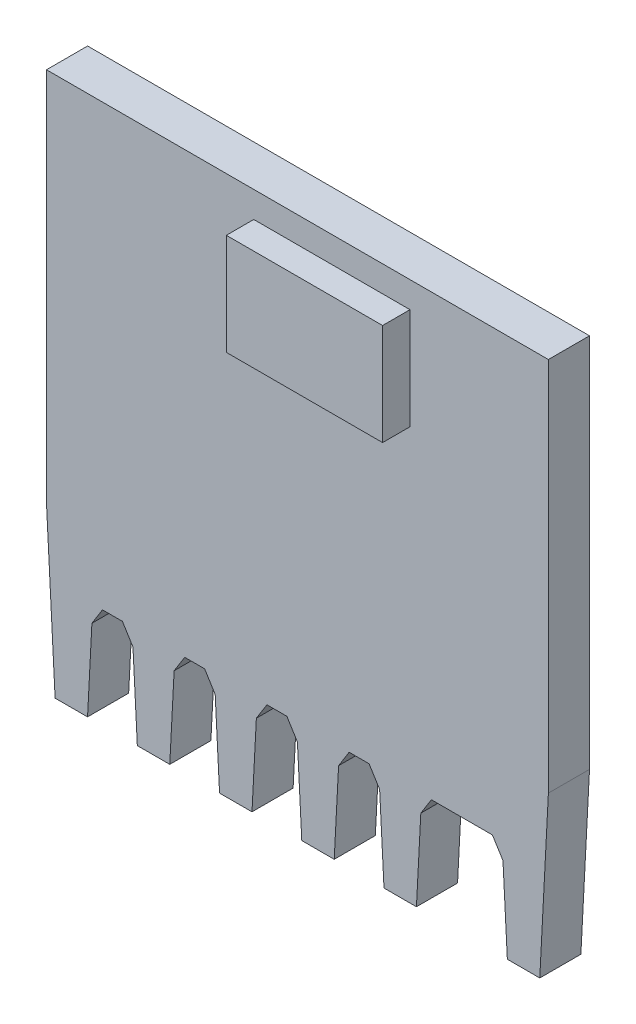
SolidWorks part; units mm, degrees
ref_plane "Front Plane" through (0, 0, 0) normal (0, 0, 1) x (1, 0, 0)
ref_plane "Top Plane" through (0, 0, 0) normal (0, 1, 0) x (1, 0, 0)
ref_plane "Right Plane" through (0, 0, 0) normal (1, 0, 0) x (0, 0, -1)
sketch "Sketch1" plane through (0, 0, 0) normal (0, 0, 1) x (1, 0, 0)
  line L0 (0, 0) -> (0, 19.7) construction
  line L1 (0, 19.7) -> (18.3124, 19.7) construction
  line L2 (18.3124, 19.7) -> (18.3124, 0) construction
  line L3 (18.3124, 0) -> (0, 0) construction
  line L4 (0, 3) -> (18.3124, 3) construction
  line L5 (0, 6) -> (18.3124, 6) construction
  line L6 (0.9062, 6) -> (0.9062, 0) construction
  line L7 (3.9062, 6) -> (3.9062, 0) construction
  line L8 (6.9062, 6) -> (6.9062, 0) construction
  line L9 (9.9062, 6) -> (9.9062, 0) construction
  line L10 (12.9062, 6) -> (12.9062, 0) construction
  line L11 (17.4062, 6) -> (17.4062, 0) construction
  line L12 (0.9062, 3) -> (3.9062, 3) construction
  line L13 (3.9062, 3) -> (6.9062, 3) construction
  line L14 (6.9062, 3) -> (9.9062, 3) construction
  line L15 (9.9062, 3) -> (12.9062, 3) construction
  line L16 (12.9062, 3) -> (17.4062, 3) construction
  line L17 (0.9062, 3) -> (0, 3) construction
  line L18 (17.4062, 3) -> (18.3124, 3) construction
  line L19 (2.4062, 3) -> (2.4062, 0) construction
  line L20 (5.4062, 3) -> (5.4062, 0) construction
  line L21 (8.4062, 3) -> (8.4062, 0) construction
  line L22 (11.4062, 3) -> (11.4062, 0) construction
  line L23 (15.1562, 3) -> (15.1562, 0) construction
  line L24 (14.4062, 3.75) -> (15.9062, 3.75) construction
  line L25 (0, 6) -> (0.3144, 0)
  line L26 (0.3144, 0) -> (1.4979, 0)
  line L27 (1.4979, 0) -> (1.6572, 3.0393)
  line L28 (3.1552, 3.0393) -> (3.3144, 0)
  line L29 (3.3144, 0) -> (4.4979, 0)
  line L30 (4.4979, 0) -> (4.6572, 3.0393)
  line L31 (6.1552, 3.0393) -> (6.3144, 0)
  line L32 (6.3144, 0) -> (7.4979, 0)
  line L33 (7.4979, 0) -> (7.6572, 3.0393)
  line L34 (9.1552, 3.0393) -> (9.3144, 0)
  line L35 (9.3144, 0) -> (10.4979, 0)
  line L36 (10.4979, 0) -> (10.6572, 3.0393)
  line L37 (12.1552, 3.0393) -> (12.3144, 0)
  line L38 (12.3144, 0) -> (13.4979, 0)
  line L39 (13.4979, 0) -> (13.6572, 3.0393)
  line L40 (16.6552, 3.0393) -> (16.8144, 0)
  line L41 (16.8144, 0) -> (17.9979, 0)
  line L42 (17.9979, 0) -> (18.3124, 6)
  line L44 (1.6572, 3.0393) -> (2.0426, 3.656)
  line L45 (0, 6) -> (0, 19.7)
  line L46 (0, 19.7) -> (18.3124, 19.7)
  line L47 (18.3124, 19.7) -> (18.3124, 6)
  line L48 (9.1562, 19.7) -> (9.1562, 6) construction
  line L49 (2.0426, 3.656) -> (2.7698, 3.656)
  line L50 (2.7698, 3.656) -> (3.1552, 3.0393)
  line L51 (4.6572, 3.0393) -> (5.0426, 3.656)
  line L52 (5.0426, 3.656) -> (5.7698, 3.656)
  line L53 (5.7698, 3.656) -> (6.1552, 3.0393)
  line L54 (7.6572, 3.0393) -> (8.0426, 3.656)
  line L55 (8.0426, 3.656) -> (8.7698, 3.656)
  line L56 (8.7698, 3.656) -> (9.1552, 3.0393)
  line L57 (10.6572, 3.0393) -> (11.0426, 3.656)
  line L58 (11.0426, 3.656) -> (11.7698, 3.656)
  line L59 (11.7698, 3.656) -> (12.1552, 3.0393)
  line L60 (13.6572, 3.0393) -> (14.0426, 3.656)
  line L61 (14.0426, 3.656) -> (16.2698, 3.656)
  line L62 (16.2698, 3.656) -> (16.6552, 3.0393)
  arc A0 (3.1552, 3.0393) -> (1.6572, 3.0393) centre (2.4062, 3) ccw construction
  arc A1 (6.1552, 3.0393) -> (4.6572, 3.0393) centre (5.4062, 3) ccw construction
  arc A2 (9.1552, 3.0393) -> (7.6572, 3.0393) centre (8.4062, 3) ccw construction
  arc A3 (12.1552, 3.0393) -> (10.6572, 3.0393) centre (11.4062, 3) ccw construction
  arc A4 (13.6572, 3.0393) -> (14.4062, 3.75) centre (14.4062, 3) cw construction
  arc A5 (16.6552, 3.0393) -> (15.9062, 3.75) centre (15.9062, 3) ccw construction
  dimension "D7" = 0.75
  dimension "D1" = 3
  dimension "D2" = 6
  dimension "D3" = 13.7
  dimension "D4" = 3
  dimension "D6" = 4.5
  dimension "D8" = 3
  dimension "D9" = 18.3124
  dimension "D10" = 19.7
extrude "Boss-Extrude1" add sketch "Sketch1" along normal blind 1.5
sketch "Sketch3" plane through (0, 0, 0) normal (0, 0, 1) x (1, 0, 0)
  line L0 (-0.4005, 6) -> (18.7129, 6)
  line L1 (18.7129, 3) -> (-0.4005, 3) construction
  line L2 (-0.4005, 0) -> (18.7129, 0) construction
  line L3 (-0.4005, -0.5) -> (18.7129, -0.5) construction
  line L4 (18.7129, -0.5) -> (18.7129, 6) construction
  line L5 (-0.4005, 6) -> (-0.4005, -0.5) construction
  line L6 (18.3124, 0) -> (0, 0) construction
  line L7 (0, 3) -> (18.3124, 3) construction
  line L8 (0, 6) -> (18.3124, 6) construction
  line L9 (0.3407, -0.5) -> (0, 6) construction
  line L10 (18.3124, 6) -> (17.9717, -0.5) construction
  line L11 (17.9979, 0) -> (18.3124, 6) construction
  line L12 (0, 6) -> (0.3144, 0) construction
  line L13 (5.4062, 6) -> (5.4062, -0.5) construction
  line L14 (3.9062, 6) -> (3.9062, -0.5) construction
  line L15 (5.4062, 3) -> (5.4062, 0) construction
  line L16 (3.1572, 3) -> (3.3407, -0.5) construction
  line L17 (2.7567, 3) -> (2.9401, -0.5)
  line L18 (3.1552, 3.0393) -> (3.3144, 0) construction
  line L19 (2.9401, -0.5) -> (4.8723, -0.5)
  line L20 (4.8723, -0.5) -> (5.0557, 3)
  line L21 (2.8484, 1.25) -> (3.2478, 1.2709) construction
  line L22 (5.9401, -0.5) -> (5.7567, 3)
  line L26 (7.8723, -0.5) -> (5.9401, -0.5)
  line L27 (8.0557, 3) -> (7.8723, -0.5)
  line L30 (2.4062, -0.5) -> (2.4062, 6) construction
  line L31 (2.4062, 3) -> (2.4062, 0) construction
  line L32 (8.4062, 6) -> (8.4062, -0.5) construction
  line L34 (11.4062, -0.5) -> (11.4062, 6) construction
  line L35 (15.1562, -0.5) -> (15.1562, 6) construction
  line L36 (8.4062, 3) -> (8.4062, 0) construction
  line L37 (11.4062, 3) -> (11.4062, 0) construction
  line L38 (15.1562, 3) -> (15.1562, 0) construction
  line L39 (10.8723, -0.5) -> (11.0557, 3)
  line L40 (8.9401, -0.5) -> (10.8723, -0.5)
  line L41 (8.7567, 3) -> (8.9401, -0.5)
  line L42 (11.9401, -0.5) -> (11.7567, 3)
  line L43 (13.8723, -0.5) -> (11.9401, -0.5)
  line L44 (14.0557, 3) -> (13.8723, -0.5)
  line L45 (16.4401, -0.5) -> (18.3723, -0.5)
  line L46 (16.2567, 3) -> (16.4401, -0.5)
  line L47 (18.3723, -0.5) -> (18.7129, 6)
  line L48 (1.8723, -0.5) -> (-0.0599, -0.5)
  line L49 (2.0557, 3) -> (1.8723, -0.5)
  line L50 (-0.0599, -0.5) -> (-0.4005, 6)
  line L51 (16.2567, 3) -> (14.0557, 3)
  line L52 (11.7567, 3) -> (11.0557, 3)
  line L53 (8.7567, 3) -> (8.0557, 3)
  line L54 (5.7567, 3) -> (5.0557, 3)
  line L55 (2.7567, 3) -> (2.0557, 3)
  dimension "D1" = 0.5
  dimension "D2" = 0.4
ref_plane "Plane1" through (3.9062, 0, 0) normal (1, 0, 0) x (0, 0, -1)
sketch "Sketch4" plane through (3.9062, 0, 0) normal (1, 0, 0) x (0, 0, -1)
  line L0 (0, 6) -> (0, -0.5) construction
  line L1 (0.6, 6) -> (-2.1, 6) construction
  line L2 (0.6, 6) -> (0.6, -0.5) construction
  line L3 (0.6, -0.5) -> (-2.1, -0.5) construction
  line L4 (-2.1, 6) -> (-2.1, -0.5) construction
  line L5 (-0.75, -0.5) -> (-0.75, 6) construction
  line L6 (-1.5, 6) -> (-1.5, -0.5) construction
  line L7 (0.6, 2.4005) -> (-2.1, 2.4005) construction
  line L8 (0.3, 6) -> (0.3, -0.5) construction
  line L9 (0.6, 2.4005) -> (3.846, 6) construction
  line L10 (2.2302, 6) -> (0.6, 4.1923) construction
  line L11 (0.6, 4.1923) -> (1.7139, 3.1878) construction
  line L12 (1.7139, 3.1878) -> (4.25, 6)
  line L13 (4.25, 6) -> (0.6, 6) construction
  line L14 (0.3, 1) -> (-1.8, 1) construction
  line L15 (-2.1, 0) -> (0.6, 0) construction
  line L16 (1.7139, 3.1878) -> (1.4912, 3.3887)
  line L17 (1.4912, 3.3887) -> (0.6, 2.4005)
  line L18 (-3.2139, 3.1878) -> (-5.75, 6)
  line L19 (-3.2139, 3.1878) -> (-2.9912, 3.3887)
  line L20 (-2.9912, 3.3887) -> (-2.1, 2.4005)
  line L21 (-2.1, 6) -> (-5.75, 6) construction
  line L22 (0.6, 3.0724) -> (3.2401, 6) construction
  arc A0 (0.4965, 2.2224) -> (0.6, -0.5) centre (4.2, 1) ccw
  arc A1 (0.6, 2.4005) -> (0.4965, 2.2224) centre (0.9713, 2.0656) ccw
  arc A2 (-2.1, 2.4005) -> (-1.9965, 2.2224) centre (-2.4713, 2.0656) cw
  arc A3 (-1.9965, 2.2224) -> (-2.1, -0.5) centre (-5.7, 1) cw
  dimension "D6" = 0.5
  dimension "D1" = 0.6
  dimension "D2" = 0.3
  dimension "D3" = 1.5
  dimension "D4" = 1
  dimension "D5" = 0.3
  dimension "D7" = 10
sketch "Sketch5" plane through (0, 0, 0) normal (1, 0, 0) x (0, 0, -1)
  line L0 (2.2302, 6) -> (0.6, 4.1923) construction
  line L1 (0.6, 4.1923) -> (1.7139, 3.1878) construction
  line L2 (1.7139, 3.1878) -> (4.25, 6) construction
  line L3 (2.2302, 6) -> (0.6, 4.1923) construction
  line L4 (0.6, 4.1923) -> (1.7139, 3.1878) construction
  line L5 (1.7139, 3.1878) -> (4.25, 6) construction
ref_plane "Plane2" through (0, 2.6105, -2.3541) normal (0, 0.7426, -0.6697) x (1, 0, 0)
sketch "Sketch6" plane through (0, 2.6105, -2.3541) normal (0, 0.7426, -0.6697) x (1, 0, 0)
  line L1 (3.9062, -2.362) -> (3.9062, -0.862) construction
  line L2 (3.9062, -2.362) -> (3.9062, -5.0612) construction
  line L3 (4.6562, -5.0612) -> (3.1562, -5.0612)
  line L4 (4.6562, -1.612) -> (3.1562, -1.612) construction
  line L5 (3.1562, -1.612) -> (3.1562, -5.0612)
  line L6 (4.6562, -1.612) -> (4.6562, -5.0612)
  line L10 (2.4062, -5.0612) -> (15.1562, -5.0612) construction
  line L11 (15.1562, -5.0612) -> (15.1562, -0.862) construction
  line L12 (15.1562, -0.862) -> (2.4062, -0.862) construction
  line L13 (2.4062, -0.862) -> (2.4062, -5.0612) construction
  line L14 (15.1562, 0.3349) -> (15.1562, -4.0182) construction
  line L15 (2.4062, 0.3349) -> (2.4062, -4.0182) construction
  line L16 (11.4062, -5.0612) -> (11.4062, -0.862) construction
  line L17 (8.4062, -5.0612) -> (8.4062, -0.862) construction
  line L18 (5.4062, -5.0612) -> (5.4062, -0.862) construction
  line L19 (5.4062, -4.0182) -> (5.4062, 0.3349) construction
  line L20 (8.4062, -4.0182) -> (8.4062, 0.3349) construction
  line L21 (11.4062, 0.3349) -> (11.4062, -4.0182) construction
  line L22 (0.1562, -1.612) -> (0.1562, -5.0612)
  line L23 (0.1562, -5.0612) -> (1.6562, -5.0612)
  line L24 (1.6562, -1.612) -> (1.6562, -5.0612)
  line L25 (7.6562, -1.612) -> (7.6562, -5.0612)
  line L26 (6.1562, -5.0612) -> (7.6562, -5.0612)
  line L27 (6.1562, -1.612) -> (6.1562, -5.0612)
  line L28 (10.6562, -1.612) -> (10.6562, -5.0612)
  line L29 (10.6562, -5.0612) -> (9.1562, -5.0612)
  line L30 (9.1562, -1.612) -> (9.1562, -5.0612)
  line L31 (13.6562, -1.612) -> (13.6562, -5.0612)
  line L32 (12.1562, -5.0612) -> (13.6562, -5.0612)
  line L33 (12.1562, -1.612) -> (12.1562, -5.0612)
  line L34 (18.1562, -1.612) -> (18.1562, -5.0612)
  line L35 (18.1562, -5.0612) -> (16.6562, -5.0612)
  line L36 (16.6562, -1.612) -> (16.6562, -5.0612)
  circle A0 centre (3.9062, -1.612) radius 0.75 construction
  arc A1 (4.6562, -1.612) -> (3.1562, -1.612) centre (3.9062, -1.612) ccw
  arc A2 (0.1562, -1.612) -> (1.6562, -1.612) centre (0.9062, -1.612) cw
  arc A3 (6.1562, -1.612) -> (7.6562, -1.612) centre (6.9062, -1.612) cw
  arc A4 (10.6562, -1.612) -> (9.1562, -1.612) centre (9.9062, -1.612) ccw
  arc A5 (12.1562, -1.612) -> (13.6562, -1.612) centre (12.9062, -1.612) cw
  arc A6 (18.1562, -1.612) -> (16.6562, -1.612) centre (17.4062, -1.612) ccw
ref_plane "Plane3" through (0, 1.6223, -1.463) normal (0, 0.7426, -0.6697) x (1, 0, 0)
sketch "Sketch7" plane through (0, 1.6223, -1.463) normal (0, 0.7426, -0.6697) x (1, 0, 0)
  line L0 (3.1562, -1.612) -> (3.1562, -5.0612) construction
  line L1 (4.6562, -5.0612) -> (3.1562, -5.0612) construction
  line L2 (4.6562, -1.612) -> (4.6562, -5.0612) construction
  line L3 (3.1562, -1.612) -> (3.1562, -5.0612) construction
  line L4 (4.6562, -5.0612) -> (3.1562, -5.0612) construction
  line L5 (4.6562, -1.612) -> (4.6562, -5.0612) construction
  line L6 (3.9062, -0.862) -> (3.9062, -5.0612) construction
  line L7 (4.6562, -1.612) -> (3.1562, -1.612) construction
  line L8 (4.6562, -2.362) -> (3.1562, -2.362) construction
  line L9 (3.4562, -1.612) -> (3.4562, -2.362)
  line L10 (3.4562, -2.362) -> (4.3562, -2.362)
  line L11 (4.3562, -2.362) -> (4.3562, -1.612)
  line L12 (2.4062, -0.862) -> (2.4062, -5.0612) construction
  line L13 (2.4062, -5.0612) -> (15.1562, -5.0612) construction
  line L14 (15.1562, -0.862) -> (2.4062, -0.862) construction
  line L15 (5.4062, -5.0612) -> (5.4062, -0.862) construction
  line L16 (8.4062, -5.0612) -> (8.4062, -0.862) construction
  line L17 (11.4062, -5.0612) -> (11.4062, -0.862) construction
  line L18 (15.1562, -5.0612) -> (15.1562, -0.862) construction
  line L19 (2.4062, -0.862) -> (2.4062, -5.0612) construction
  line L20 (2.4062, -5.0612) -> (15.1562, -5.0612) construction
  line L21 (15.1562, -0.862) -> (2.4062, -0.862) construction
  line L22 (5.4062, -5.0612) -> (5.4062, -0.862) construction
  line L23 (8.4062, -5.0612) -> (8.4062, -0.862) construction
  line L24 (11.4062, -5.0612) -> (11.4062, -0.862) construction
  line L25 (15.1562, -5.0612) -> (15.1562, -0.862) construction
  line L26 (0.4562, -2.362) -> (0.4562, -1.612)
  line L27 (1.3562, -2.362) -> (0.4562, -2.362)
  line L28 (1.3562, -1.612) -> (1.3562, -2.362)
  line L29 (7.3562, -2.362) -> (6.4562, -2.362)
  line L30 (7.3562, -1.612) -> (7.3562, -2.362)
  line L31 (6.4562, -2.362) -> (6.4562, -1.612)
  line L32 (9.4562, -1.612) -> (9.4562, -2.362)
  line L33 (10.3562, -2.362) -> (10.3562, -1.612)
  line L34 (9.4562, -2.362) -> (10.3562, -2.362)
  line L35 (13.3562, -1.612) -> (13.3562, -2.362)
  line L36 (12.4562, -2.362) -> (12.4562, -1.612)
  line L37 (13.3562, -2.362) -> (12.4562, -2.362)
  line L38 (16.9562, -1.612) -> (16.9562, -2.362)
  line L39 (17.8562, -2.362) -> (17.8562, -1.612)
  line L40 (16.9562, -2.362) -> (17.8562, -2.362)
  arc A0 (4.6562, -1.612) -> (3.1562, -1.612) centre (3.9062, -1.612) ccw construction
  arc A1 (4.6562, -1.612) -> (3.1562, -1.612) centre (3.9062, -1.612) ccw construction
  circle A2 centre (3.9062, -1.612) radius 0.45 construction
  arc A3 (4.3562, -1.612) -> (3.4562, -1.612) centre (3.9062, -1.612) ccw
  arc A4 (0.4562, -1.612) -> (1.3562, -1.612) centre (0.9062, -1.612) cw
  arc A5 (6.4562, -1.612) -> (7.3562, -1.612) centre (6.9062, -1.612) cw
  arc A6 (10.3562, -1.612) -> (9.4562, -1.612) centre (9.9062, -1.612) ccw
  arc A7 (12.4562, -1.612) -> (13.3562, -1.612) centre (12.9062, -1.612) cw
  arc A8 (17.8562, -1.612) -> (16.9562, -1.612) centre (17.4062, -1.612) ccw
ref_plane "bisect" through (0, 0, 0.75) normal (0, 0, 1) x (1, 0, 0)
ref_plane "insert_surface" through (0, 6, 0) normal (0, 1, 0) x (1, 0, 0)
sketch "Sketch8" plane through (0, 6, 0) normal (0, 1, 0) x (1, 0, 0)
  line L0 (18.7129, -0.75) -> (-0.4005, -0.75) construction
  line L1 (-0.4005, 0.6) -> (18.7129, 0.6)
  line L2 (-0.4005, 0.6) -> (-0.4005, -2.1)
  line L3 (-0.4005, -2.1) -> (18.7129, -2.1)
  line L4 (18.7129, 0.6) -> (18.7129, -2.1)
  line L5 (9.1562, 0.6) -> (9.1562, -2.1) construction
  line L6 (0, 0) -> (18.3124, 0) construction
  line L7 (0, 0) -> (0, -1.5) construction
  line L8 (0, -1.5) -> (18.3124, -1.5) construction
  line L9 (18.3124, 0) -> (18.3124, -1.5) construction
  line L10 (18.7129, 0.3) -> (-0.4005, 0.3) construction
  line L11 (18.7129, -1.8) -> (-0.4005, -1.8) construction
sketch "Sketch9" plane through (0, 0, 0) normal (0, 0, 1) x (1, 0, 0)
  line L0 (18.3723, -0.5) -> (18.7129, 6) construction
  line L1 (-0.4005, 6) -> (18.7129, 6) construction
  line L2 (-0.0599, -0.5) -> (-0.4005, 6) construction
  line L3 (1.8723, -0.5) -> (-0.0599, -0.5) construction
  line L4 (2.0557, 3) -> (1.8723, -0.5) construction
  line L5 (2.7567, 3) -> (2.0557, 3) construction
  line L6 (2.7567, 3) -> (2.9401, -0.5) construction
  line L7 (2.9401, -0.5) -> (4.8723, -0.5) construction
  line L8 (4.8723, -0.5) -> (5.0557, 3) construction
  line L9 (5.7567, 3) -> (5.0557, 3) construction
  line L10 (5.9401, -0.5) -> (5.7567, 3) construction
  line L11 (7.8723, -0.5) -> (5.9401, -0.5) construction
  line L12 (8.0557, 3) -> (7.8723, -0.5) construction
  line L13 (8.7567, 3) -> (8.0557, 3) construction
  line L14 (8.7567, 3) -> (8.9401, -0.5) construction
  line L15 (8.9401, -0.5) -> (10.8723, -0.5) construction
  line L16 (10.8723, -0.5) -> (11.0557, 3) construction
  line L17 (11.7567, 3) -> (11.0557, 3) construction
  line L18 (11.9401, -0.5) -> (11.7567, 3) construction
  line L19 (13.8723, -0.5) -> (11.9401, -0.5) construction
  line L20 (14.0557, 3) -> (13.8723, -0.5) construction
  line L21 (16.2567, 3) -> (14.0557, 3) construction
  line L22 (16.2567, 3) -> (16.4401, -0.5) construction
  line L23 (16.4401, -0.5) -> (18.3723, -0.5) construction
  line L24 (18.3723, -0.5) -> (18.7129, 6)
  line L25 (-0.4005, 6) -> (18.7129, 6) construction
  line L26 (-0.0599, -0.5) -> (-0.4005, 6)
  line L27 (1.8723, -0.5) -> (-0.0599, -0.5)
  line L28 (2.0557, 3) -> (1.8723, -0.5)
  line L29 (2.7567, 3) -> (2.0557, 3) construction
  line L30 (2.7567, 3) -> (2.9401, -0.5)
  line L31 (2.9401, -0.5) -> (4.8723, -0.5)
  line L32 (4.8723, -0.5) -> (5.0557, 3)
  line L33 (5.7567, 3) -> (5.0557, 3) construction
  line L34 (5.9401, -0.5) -> (5.7567, 3)
  line L35 (7.8723, -0.5) -> (5.9401, -0.5)
  line L36 (8.0557, 3) -> (7.8723, -0.5)
  line L37 (8.7567, 3) -> (8.0557, 3) construction
  line L38 (8.7567, 3) -> (8.9401, -0.5)
  line L39 (8.9401, -0.5) -> (10.8723, -0.5)
  line L40 (10.8723, -0.5) -> (11.0557, 3)
  line L41 (11.7567, 3) -> (11.0557, 3) construction
  line L42 (11.9401, -0.5) -> (11.7567, 3)
  line L43 (13.8723, -0.5) -> (11.9401, -0.5)
  line L44 (14.0557, 3) -> (13.8723, -0.5)
  line L45 (16.2567, 3) -> (14.0557, 3) construction
  line L46 (16.2567, 3) -> (16.4401, -0.5)
  line L47 (16.4401, -0.5) -> (18.3723, -0.5)
  line L48 (16.2567, 3) -> (16.2567, 6)
  line L49 (14.0557, 3) -> (14.0557, 6)
  line L50 (11.7567, 3) -> (11.7567, 6)
  line L51 (18.7129, 6) -> (-0.4005, 6) construction
  line L52 (11.0557, 3) -> (11.0557, 6)
  line L53 (-0.4005, 6) -> (18.7129, 6) construction
  line L54 (8.7567, 3) -> (8.7567, 6)
  line L55 (8.0557, 3) -> (8.0557, 6)
  line L58 (5.7567, 3) -> (5.7567, 6)
  line L60 (5.0557, 3) -> (5.0557, 6)
  line L62 (15.1562, -0.5) -> (15.1562, 6) construction
  line L63 (15.1562, -0.5) -> (15.1562, 6) construction
  line L64 (2.7567, 3) -> (2.7567, 6)
  line L65 (2.0557, 3) -> (2.0557, 6)
  line L67 (18.7129, 6) -> (16.2567, 6)
  line L68 (14.0557, 6) -> (11.7567, 6)
  line L69 (11.0557, 6) -> (8.7567, 6)
  line L70 (8.0557, 6) -> (5.7567, 6)
  line L71 (5.0557, 6) -> (2.7567, 6)
  line L72 (2.0557, 6) -> (-0.4005, 6)
sketch "rgb_led" plane through (0, 0, 1.5) normal (0, 0, 1) x (1, 0, 0)
  line L0 (13.2624, 16.9) -> (7.5624, 16.9) construction
  line L1 (0, 6) -> (18.3124, 6) construction
  line L2 (10.4124, 16.9) -> (10.4124, 15.05) construction
  line L3 (10.4124, 19.7) -> (10.4124, 16.9) construction
  line L4 (18.3124, 19.7) -> (18.3124, 6) construction
  line L5 (0, 6) -> (0, 19.7) construction
  line L6 (13.2624, 18.75) -> (7.5624, 18.75)
  line L7 (13.2624, 18.75) -> (13.2624, 15.05)
  line L8 (13.2624, 15.05) -> (7.5624, 15.05)
  line L9 (7.5624, 18.75) -> (7.5624, 15.05)
  line L10 (0, 19.7) -> (18.3124, 19.7) construction
  line L11 (0, 19.7) -> (18.3124, 19.7) construction
  line L16 (0, 6) -> (18.3124, 6) construction
  line L17 (18.3124, 6) -> (18.3124, 19.7) construction
  line L18 (0, 19.7) -> (0, 6) construction
  dimension "D1" = 2.8
  dimension "D2" = 3.7
  dimension "D3" = 5.7
  dimension "D4" = 7.9
extrude "Boss-Extrude2" add sketch "rgb_led" along normal blind 1
sketch "Sketch10" plane through (0, 6, 0) normal (0, 1, 0) x (1, 0, 0)
  line L0 (-0.8438, -0.75) -> (9.1562, -0.75) construction
  line L1 (-0.8438, 4.25) -> (19.1562, 4.25)
  line L2 (-0.8438, 4.25) -> (-0.8438, -5.75)
  line L3 (-0.8438, -5.75) -> (19.1562, -5.75)
  line L4 (19.1562, 4.25) -> (19.1562, -5.75)
  line L5 (9.1562, -0.75) -> (19.1562, -0.75) construction
  line L6 (9.1562, -0.75) -> (9.1562, 4.25) construction
  line L7 (9.1562, -0.75) -> (9.1562, -5.75) construction
  line L8 (-10.5124, -0.75) -> (10.5124, -0.75) construction
  dimension "D1" = 10
  dimension "D2" = 20
